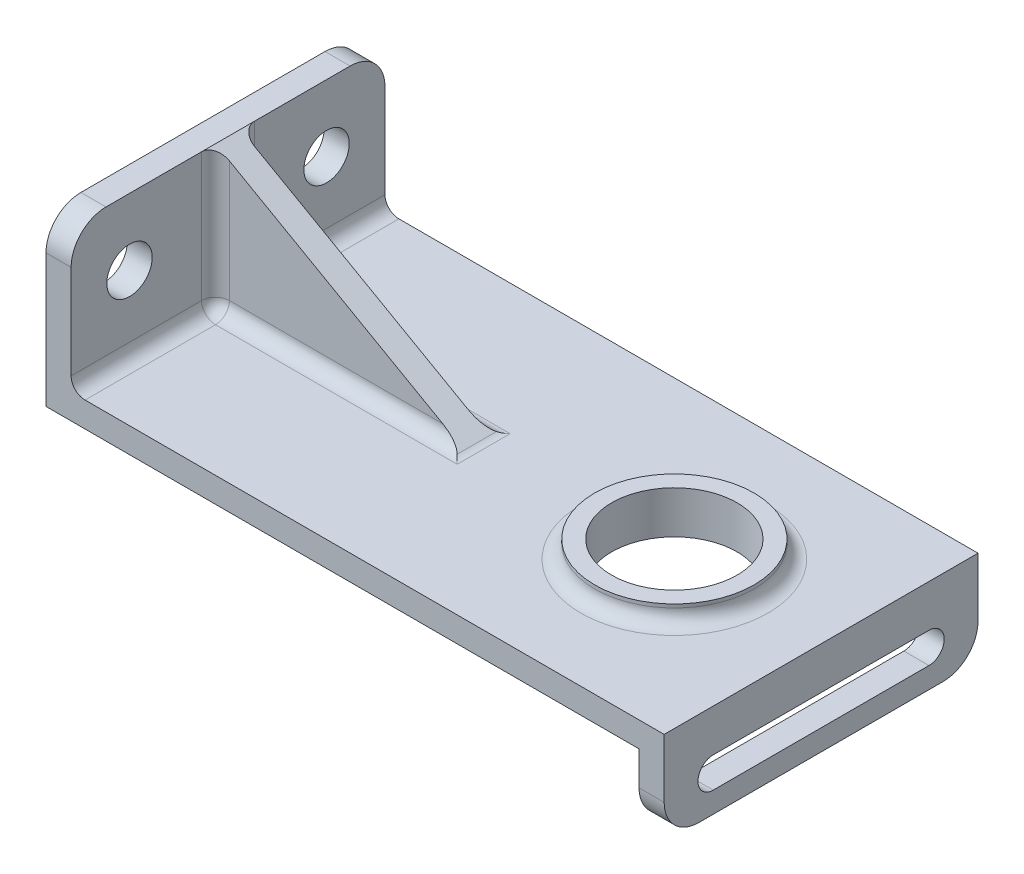
SolidWorks part; units mm, degrees
ref_plane "Front Plane" through (0, 0, 0) normal (0, 0, 1) x (1, 0, 0)
ref_plane "Top Plane" through (0, 0, 0) normal (0, 1, 0) x (1, 0, 0)
ref_plane "Right Plane" through (0, 0, 0) normal (1, 0, 0) x (0, 0, -1)
sketch "Sketch1" plane through (0, 0, 0) normal (0, 0, 1) x (1, 0, 0)
  line L0 (0, 30.577) -> (0, 0)
  line L1 (0, 0) -> (107.99, 0)
  line L2 (107.99, 0) -> (107.99, -12.4967)
  line L3 (4.572, 30.577) -> (4.572, 4.572)
  line L4 (4.572, 4.572) -> (112.562, 4.572)
  line L5 (112.562, 4.572) -> (112.562, -12.4967)
  line L6 (0, 30.577) -> (4.572, 30.577)
  line L7 (107.99, -12.4967) -> (112.562, -12.4967)
extrude "Extrude1" add sketch "Sketch1" along normal blind 57.15
ref_plane "Plane1" through (0, 4.572, 0) normal (0, 1, 0) x (-1, 0, 0)
sketch "Sketch2" plane through (0, 4.572, 0) normal (0, 1, 0) x (-1, 0, 0)
  line L0 (-112.562, 28.575) -> (-85.8466, 28.575) construction
  line L1 (-112.562, 57.15) -> (-112.562, 0) construction
  circle A0 centre (-85.8466, 28.575) radius 14.5064
extrude "Extrude2" add sketch "Sketch2" along normal blind 3.175
fillet "Fillet1" radius 2.54 1 edges at (85.8466, 4.572, 14.0686)
ref_plane "Plane2" through (0, 7.747, 0) normal (0, 1, 0) x (-1, 0, 0)
sketch "Sketch3" plane through (0, 7.747, 0) normal (0, 1, 0) x (-1, 0, 0)
  circle A2 centre (-85.8466, 28.575) radius 11.4214
extrude "Extrude3" cut sketch "Sketch3" against normal blind 15.875
ref_plane "Plane3" through (0, 0, 28.575) normal (0, 0, 1) x (1, 0, 0)
sketch "Sketch4" plane through (0, 0, 28.575) normal (0, 0, 1) x (1, 0, 0)
  line L0 (4.572, 30.577) -> (50.4513, 4.572)
  line L1 (31.4325, 4.572) -> (-31.4325, 4.572) construction
  line L2 (50.4513, 4.572) -> (4.572, 4.572)
  line L3 (4.572, 4.572) -> (4.572, 30.577) construction
  line L4 (4.572, 4.572) -> (4.572, 30.577)
extrude "Extrude4" add sketch "Sketch4" along normal mid plane 4.572
fillet "Fillet4" radius 2.54 7 edges at (4.572, 4.572, 13.1445) (4.572, 4.572, 44.0055) (4.572, 17.5745, 30.861) (4.572, 17.5745, 26.289) (27.5117, 4.572, 26.289) (50.4513, 4.572, 28.575) (27.5117, 4.572, 30.861)
fillet "Fillet5" radius 6.35 4 edges at (110.276, -12.4967, 0) (110.276, -12.4967, 57.15) (2.286, 30.577, 0) (2.286, 30.577, 57.15)
ref_plane "Plane4" through (112.562, 0, 0) normal (1, 0, 0) x (0, 0, -1)
sketch "Sketch5" plane through (112.562, 0, 0) normal (1, 0, 0) x (0, 0, -1)
  line L0 (-57.15, -5.9066) -> (0, -5.9066) construction
  line L1 (-57.15, -6.1467) -> (-57.15, 4.572) construction
  line L2 (0, -6.1467) -> (0, 4.572) construction
  line L3 (-48.2162, -5.9066) -> (-8.9338, -5.9066) construction
  line L4 (-48.2162, -3.13) -> (-8.9338, -3.13)
  line L5 (-48.2162, -8.6832) -> (-8.9338, -8.6832)
  arc A0 (-48.2162, -3.13) -> (-48.2162, -8.6832) centre (-48.2162, -5.9066) ccw
  arc A1 (-8.9338, -8.6832) -> (-8.9338, -3.13) centre (-8.9338, -5.9066) ccw
  point P8 (-28.575, -5.9066)
  dimension "D1" = 5.5532
  dimension "D2" = 39.2824
extrude "Extrude5" cut sketch "Sketch5" against normal blind 4.572
ref_plane "Plane5" through (4.572, 0, 0) normal (1, 0, 0) x (0, 0, -1)
sketch "Sketch6" plane through (4.572, 0, 0) normal (1, 0, 0) x (0, 0, -1)
  circle A0 centre (-46.5131, 18.432) radius 4.1341
  circle A1 centre (-10.6369, 18.432) radius 4.1341
extrude "Extrude6" cut sketch "Sketch6" against normal blind 4.572
